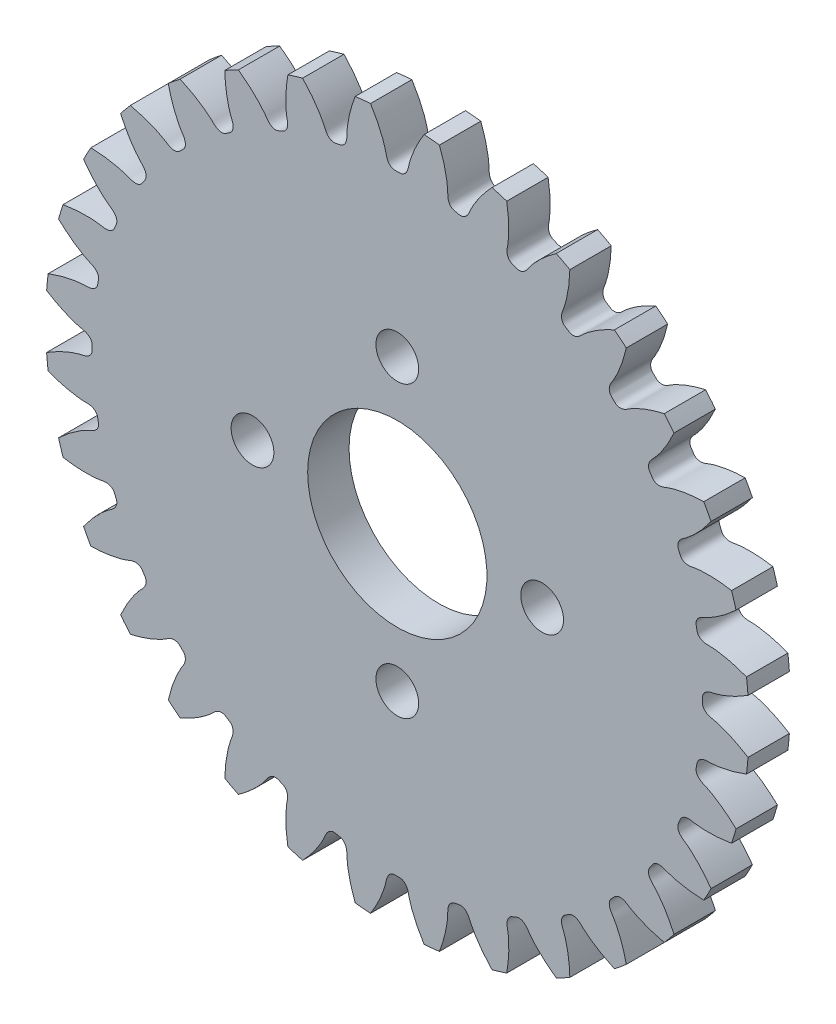
SolidWorks part; units mm, degrees
material "玻纤板"
ref_plane "前视基准面" through (0, 0, 0) normal (0, 0, 1) x (1, 0, 0)
ref_plane "上视基准面" through (0, 0, 0) normal (0, 1, 0) x (1, 0, 0)
ref_plane "右视基准面" through (0, 0, 0) normal (1, 0, 0) x (0, 0, -1)
ref_axis "基准轴1" through (0, 0, 55) along (0, 0, -1)
sketch "旋转草图小直齿轮" plane through (0, 0, 0) normal (1, 0, 0) x (0, 0, -1)
  line L0 (0, 0) -> (1, 0) construction
  line L1 (-10, 0) -> (-10, 25.5)
  line L2 (-10, 25.5) -> (-7, 25.5)
  line L3 (-7, 25.5) -> (-7, 0)
  line L4 (-7, 0) -> (-10, 0)
  dimension "D1" = 25.5
  dimension "D2" = 3
revolve "小直齿轮" add sketch "旋转草图小直齿轮" angle 360 about L0
sketch "齿草图小直齿轮" plane through (0, 0, 0) normal (0, 0, 1) x (1, 0, 0)
  arc A0 (25.4975, 1.9898) -> (25.4975, -1.9898) centre (0, 0) cw
  spline S0 degree 3 poles (25.4975, -1.9898) (25.4338, -1.9491) (25.349, -1.8959) (25.2428, -1.8313) (25.1803, -1.7938) (25.1185, -1.7573) (25.0572, -1.7215) (24.9964, -1.6867) (24.9363, -1.6526) (24.8767, -1.6194) (24.8177, -1.5871) (24.7593, -1.5555) (24.7016, -1.5247) (24.6444, -1.4948) (24.5879, -1.4656) (24.532, -1.4372) (24.4767, -1.4096) (24.4221, -1.3827) (24.3682, -1.3566) (24.3149, -1.3312) (24.2623, -1.3065) (24.2103, -1.2826) (24.1591, -1.2593) (24.1085, -1.2368) (24.0586, -1.215) (24.0095, -1.1938) (23.961, -1.1733) (23.9133, -1.1535) (23.8663, -1.1343) (23.82, -1.1158) (23.7744, -1.0979) (23.7296, -1.0806) (23.6856, -1.0639) (23.6423, -1.0479) (23.5997, -1.0324) (23.5579, -1.0175) (23.5169, -1.0032) (23.4767, -0.9894) (23.4373, -0.9762) (23.3986, -0.9635) (23.3607, -0.9513) (23.3237, -0.9397) (23.2874, -0.9285) (23.252, -0.9179) (23.2173, -0.9077) (23.1835, -0.8981) (23.1505, -0.8888) (23.1183, -0.8801) (23.087, -0.8717) (23.0565, -0.8638) (23.0268, -0.8564) (22.998, -0.8493) (22.97, -0.8426) (22.9429, -0.8363) (22.9166, -0.8304) (22.8912, -0.8249) (22.8232, -0.8105) (22.7488, -0.796) (22.67, -0.7735) (22.6281, -0.7602) (22.587, -0.7455) (22.5467, -0.7294) (22.5068, -0.7115) (22.4674, -0.6916) (22.4282, -0.6693) (22.3891, -0.6441) (22.35, -0.6152) (22.311, -0.5819) (22.2722, -0.543) (22.2344, -0.4975) (22.1988, -0.4441) (22.1673, -0.3822) (22.1425, -0.312) (22.1279, -0.2389) (22.1219, -0.134) (22.1272, 0) (22.1219, 0.134) (22.1279, 0.2389) (22.1425, 0.312) (22.1673, 0.3822) (22.1988, 0.4441) (22.2344, 0.4975) (22.2722, 0.543) (22.311, 0.5819) (22.35, 0.6152) (22.3891, 0.6441) (22.4282, 0.6693) (22.4674, 0.6916) (22.5068, 0.7115) (22.5467, 0.7294) (22.587, 0.7455) (22.6281, 0.7602) (22.67, 0.7735) (22.7488, 0.796) (22.8232, 0.8105) (22.8912, 0.8249) (22.9166, 0.8304) (22.9429, 0.8363) (22.97, 0.8426) (22.998, 0.8493) (23.0268, 0.8564) (23.0565, 0.8638) (23.087, 0.8717) (23.1183, 0.8801) (23.1505, 0.8888) (23.1835, 0.8981) (23.2173, 0.9077) (23.252, 0.9179) (23.2874, 0.9285) (23.3237, 0.9397) (23.3607, 0.9513) (23.3986, 0.9635) (23.4373, 0.9762) (23.4767, 0.9894) (23.5169, 1.0032) (23.5579, 1.0175) (23.5997, 1.0324) (23.6423, 1.0479) (23.6856, 1.0639) (23.7296, 1.0806) (23.7744, 1.0979) (23.82, 1.1158) (23.8663, 1.1343) (23.9133, 1.1535) (23.961, 1.1733) (24.0095, 1.1938) (24.0586, 1.215) (24.1085, 1.2368) (24.1591, 1.2593) (24.2103, 1.2826) (24.2623, 1.3065) (24.3149, 1.3312) (24.3682, 1.3566) (24.4221, 1.3827) (24.4767, 1.4096) (24.532, 1.4372) (24.5879, 1.4656) (24.6444, 1.4948) (24.7016, 1.5247) (24.7593, 1.5555) (24.8177, 1.5871) (24.8767, 1.6194) (24.9363, 1.6526) (24.9964, 1.6867) (25.0572, 1.7215) (25.1185, 1.7573) (25.1803, 1.7938) (25.2428, 1.8313) (25.349, 1.8959) (25.4338, 1.9491) (25.4975, 1.9898) knots 0 0 0 0 0.027364 0.036264 0.045053 0.053731 0.062299 0.070756 0.079102 0.087337 0.095462 0.103476 0.111379 0.119171 0.126853 0.134423 0.141884 0.149233 0.156471 0.163599 0.170616 0.177523 0.184318 0.191003 0.197577 0.20404 0.210393 0.216635 0.222766 0.228786 0.234696 0.240494 0.246182 0.25176 0.257226 0.262582 0.267827 0.272961 0.277985 0.282898 0.2877 0.292391 0.296972 0.301441 0.3058 0.310049 0.314186 0.318213 0.322129 0.325934 0.329629 0.333212 0.336685 0.340048 0.343299 0.34644 0.34947 0.368481 0.373854 0.379156 0.384411 0.389648 0.394901 0.400213 0.405634 0.411227 0.417063 0.423228 0.429816 0.436924 0.444637 0.453005 0.462012 0.471545 0.4799 0.5 0.5201 0.528455 0.537988 0.546995 0.555363 0.563076 0.570184 0.576772 0.582937 0.588773 0.594366 0.599787 0.605099 0.610352 0.615589 0.620844 0.626146 0.631519 0.65053 0.65356 0.656701 0.659952 0.663315 0.666788 0.670371 0.674066 0.677871 0.681787 0.685814 0.689951 0.6942 0.698559 0.703028 0.707609 0.7123 0.717102 0.722015 0.727039 0.732173 0.737418 0.742774 0.74824 0.753818 0.759506 0.765304 0.771214 0.777234 0.783365 0.789607 0.79596 0.802423 0.808997 0.815682 0.822477 0.829384 0.836401 0.843529 0.850767 0.858116 0.865577 0.873147 0.880829 0.888621 0.896524 0.904538 0.912663 0.920898 0.929244 0.937701 0.946269 0.954947 0.963736 0.972636 1 1 1 1
extrude "齿拉伸切除小直齿轮" cut sketch "齿草图小直齿轮" against normal blind 10 and the other way blind 10
pattern_circular "齿形小直齿轮" count 32 every 11.25 about axis through (0, 0, 55) along (0, 0, -1) of "齿拉伸切除小直齿轮"
sketch "辅助草图小直齿轮" plane through (0, 0, 0) normal (0, 0, 1) x (1, 0, 0)
  circle A0 centre (0, 0) radius 24 construction
  circle A1 centre (0, 0) radius 22.5526 construction
  circle A2 centre (0, 0) radius 22.8369 construction
  circle A3 centre (0, 0) radius 25.5 construction
  circle A4 centre (0, 0) radius 22.125 construction
  dimension "PitchDiameter" = 48
  dimension "BaseDiameter" = 45.1052
  dimension "FormDiameter" = 45.6738
  dimension "MajorDiameter" = 51
  dimension "MinorDiameter" = 44.25
sketch "草图1" plane through (0, 0, 7) normal (0, 0, -1) x (-1, 0, 0)
  circle A0 centre (0, 0) radius 6.5
  circle A1 centre (0, 0) radius 10.5 construction
  circle A2 centre (0, 10.5) radius 1.55
  circle A3 centre (10.5, 0) radius 1.55
  circle A4 centre (0, -10.5) radius 1.55
  circle A5 centre (-10.5, 0) radius 1.55
  point P14 (0, 0)
  dimension "D1" = 13
  dimension "D2" = 21
  dimension "D3" = 3.1
  dimension "D4" = 4
extrude "切除-拉伸1" cut sketch "草图1" against normal blind 10
